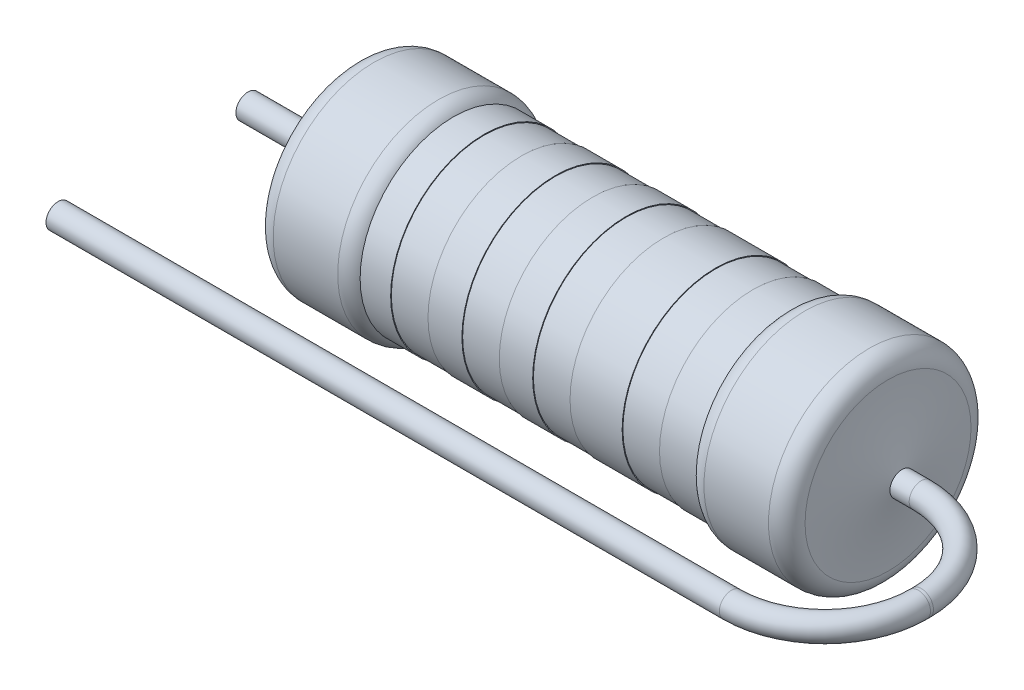
SolidWorks part; units mm, degrees
ref_plane "Front Plane" through (0, 0, 0) normal (0, 0, 1) x (1, 0, 0)
ref_plane "Top Plane" through (0, 0, 0) normal (0, 1, 0) x (1, 0, 0)
ref_plane "Right Plane" through (0, 0, 0) normal (1, 0, 0) x (0, 0, -1)
sketch "Sketch3" plane through (0, 0, 0) normal (0, 0, 1) x (1, 0, 0)
  line L0 (-9.0282, 0) -> (9.6434, 0) construction
  line L1 (-7.1192, 2.7) -> (-4.5, 2.7)
  line L2 (-4.5, 2.7) -> (-4.5, 2.5)
  line L3 (-4.5, 2.5) -> (-3.684, 2.5)
  line L4 (-2.684, 2.5) -> (-1.7768, 2.5)
  line L5 (4.5, 2.5) -> (4.5, 2.7)
  line L6 (4.5, 2.7) -> (7.1192, 2.7)
  line L8 (7.5, 0) -> (-7.5, 0)
  line L9 (-0.7768, 2.5) -> (0.1169, 2.5)
  line L10 (-3.684, 2.5) -> (-3.684, 2.48)
  line L11 (-3.684, 2.48) -> (-2.684, 2.48)
  line L12 (-2.684, 2.5) -> (-2.684, 2.48)
  line L13 (1.1169, 2.5) -> (2.511, 2.5)
  line L14 (-1.7768, 2.5) -> (-1.7768, 2.48)
  line L15 (-1.7768, 2.48) -> (-0.7768, 2.48)
  line L16 (-0.7768, 2.5) -> (-0.7768, 2.48)
  line L17 (3.511, 2.5) -> (4.5, 2.5)
  line L18 (0.1169, 2.5) -> (0.1169, 2.48)
  line L19 (0.1169, 2.48) -> (1.1169, 2.48)
  line L20 (1.1169, 2.5) -> (1.1169, 2.48)
  line L22 (2.511, 2.5) -> (2.511, 2.48)
  line L23 (2.511, 2.48) -> (3.511, 2.48)
  line L24 (3.511, 2.5) -> (3.511, 2.48)
  spline S0 degree 2 poles (-7.1192, 2.7) (-7.1029, 1.3252) (-7.5, 0) knots 0 0 0 1 1 1
  spline S1 degree 2 poles (7.1192, 2.7) (7.1029, 1.3252) (7.5, 0) knots 0 0 0 1 1 1
  dimension "D2" = 9
  dimension "D3" = 4.5
  dimension "D5" = 2.5
  dimension "D6" = 2.7
  dimension "D8" = 1
  dimension "D9" = 1
  dimension "D10" = 1
  dimension "D11" = 1
  dimension "D12" = 0.02
  dimension "D13" = 0.02
  dimension "D14" = 0.02
  dimension "D15" = 0.02
revolve "Revolve1" add sketch "Sketch3" angle 360 about L0
fillet "Fillet1" radius 0.5 2 edges at (7.1192, -2.7, 0) (-7.1192, -2.7, 0)
fillet "Fillet2" radius 0.5 2 edges at (-4.5, -2.7, 0) (4.5, -2.7, 0)
sketch "Sketch5" plane through (0, 0, 0) normal (0, 1, 0) x (1, 0, 0)
  line L0 (-9.5, -5) -> (-9.5, -1.5)
  line L1 (-8, 0) -> (8, 0)
  line L2 (9.5, -1.5) -> (9.5, -5)
  arc A0 (8, 0) -> (9.5, -1.5) centre (8, -1.5) cw
  arc A1 (-9.5, -1.5) -> (-8, 0) centre (-8, -1.5) cw
  point P7 (9.5, 0)
  point P10 (-9.5, 0)
  dimension "D5" = 1.5
  dimension "D1" = 19
  dimension "D2" = 9.5
  dimension "D3" = 5
  dimension "D4" = 5
ref_plane "Plane1" through (0, 0, 5) normal (0, 0, 1) x (1, 0, 0)
sketch "Sketch6" plane through (0, 0, 5) normal (0, 0, 1) x (1, 0, 0)
  circle A0 centre (9.5, 0) radius 0.4
  dimension "D1" = 0.8
ref_plane "Plane2" through (-7.5, 0, 0) normal (1, 0, 0) x (0, 0, -1)
sketch "Sketch8" plane through (-7.5, 0, 0) normal (1, 0, 0) x (0, 0, -1)
  circle A0 centre (0, 0) radius 0.325
  dimension "D1" = 0.65
extrude "Boss-Extrude1" add sketch "Sketch8" along normal blind 2 and the other way blind 2.5
sketch "Sketch9" plane through (0, 0, 0) normal (0, 1, 0) x (1, 0, 0)
  line L0 (7.5, 0) -> (8.0167, 0)
  line L1 (10.5167, -2.5) -> (10.5167, -2.58)
  line L2 (8.0167, -5.08) -> (-10, -5.08)
  arc A0 (8.0167, 0) -> (10.5167, -2.5) centre (8.0167, -2.5) cw
  arc A1 (8.0167, -5.08) -> (10.5167, -2.58) centre (8.0167, -2.58) ccw
  dimension "D2" = 2.5
  dimension "D1" = 5.08
ref_plane "Plane3" through (7.5, 0, 0) normal (1, 0, 0) x (0, 0, -1)
sketch "Sketch10" plane through (7.5, 0, 0) normal (1, 0, 0) x (0, 0, -1)
  circle A0 centre (0, 0) radius 0.325
  dimension "D1" = 0.65
sweep "Sweep1" add profiles "Sketch10" path "Sketch9"
